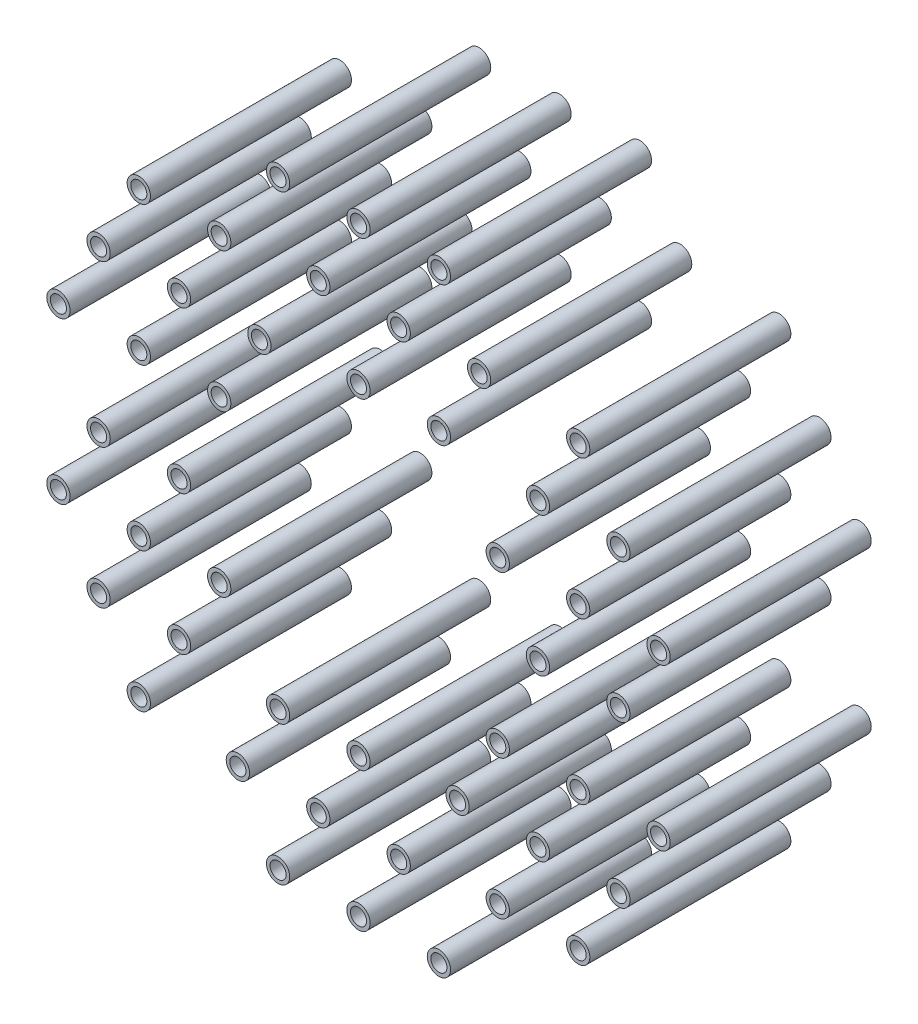
SolidWorks part; units mm, degrees
ref_plane "Front Plane" through (0, 0, 0) normal (0, 0, 1) x (1, 0, 0)
ref_plane "Top Plane" through (0, 0, 0) normal (0, 1, 0) x (1, 0, 0)
ref_plane "Right Plane" through (0, 0, 0) normal (1, 0, 0) x (0, 0, -1)
sketch "Sketch1" plane through (0, 0, 0) normal (0, 0, 1) x (1, 0, 0)
  line L0 (0, 10.16) -> (-2.54, 14.5594) construction
  line L1 (-2.54, 14.5594) -> (2.54, 14.5594) construction
  line L2 (2.54, 14.5594) -> (0, 10.16) construction
  line L3 (2.54, 14.5594) -> (0, 18.9588) construction
  line L4 (0, 18.9588) -> (-2.54, 14.5594) construction
  line L5 (-2.54, 14.5594) -> (-5.08, 18.9588) construction
  line L6 (-5.08, 18.9588) -> (0, 18.9588) construction
  line L7 (0, 10.16) -> (5.08, 10.16) construction
  line L8 (5.08, 10.16) -> (2.54, 14.5594) construction
  line L9 (2.54, 14.5594) -> (7.62, 14.5594) construction
  line L10 (7.62, 14.5594) -> (5.08, 10.16) construction
  line L11 (2.54, 14.5594) -> (5.08, 18.9588) construction
  line L12 (5.08, 18.9588) -> (0, 18.9588) construction
  line L13 (7.62, 14.5594) -> (5.08, 18.9588) construction
  line L14 (0, 10.16) -> (0, 0) construction
  circle A0 centre (0, 10.16) radius 0.7366
  circle A1 centre (0, 10.16) radius 0.508
  circle A2 centre (5.08, 10.16) radius 0.7366
  circle A3 centre (5.08, 10.16) radius 0.508
  circle A4 centre (7.62, 14.5594) radius 0.7366
  circle A5 centre (7.62, 14.5594) radius 0.508
  circle A6 centre (2.54, 14.5594) radius 0.7366
  circle A7 centre (2.54, 14.5594) radius 0.508
  circle A8 centre (-2.54, 14.5594) radius 0.7366
  circle A9 centre (-2.54, 14.5594) radius 0.508
  circle A10 centre (0, 18.9588) radius 0.7366
  circle A11 centre (0, 18.9588) radius 0.508
  circle A12 centre (5.08, 18.9588) radius 0.7366
  circle A13 centre (5.08, 18.9588) radius 0.508
  circle A14 centre (-5.08, 18.9588) radius 0.7366
  circle A15 centre (-5.08, 18.9588) radius 0.508
  point P25 (2.54, 14.5594)
  dimension "Injector Needles Inner Diameter" = 1.016
  dimension "Injector Needles Outer Diameter" = 1.4732
  dimension "Distance Between Needles" = 5.08
  dimension "1st Hole Distance From Center" = 10.16
extrude "Boss-Extrude1" add sketch "Sketch1" along normal blind 12.7
ref_axis "Axis1" through (0, 0, 13.335) along (0, 0, -1)
pattern_circular "CirPattern2" count 6 over 360 about axis through (0, 0, 13.335) along (0, 0, -1) of bodies 108 107 106 105 104 103 102 101
